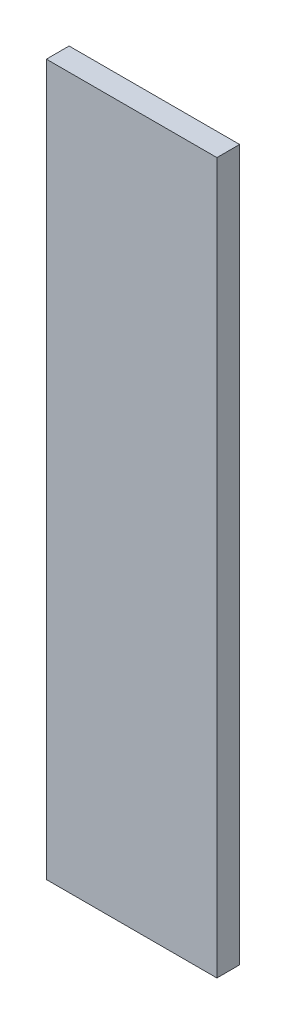
SolidWorks part; units mm, degrees
ref_plane "Alzado" through (0, 0, 0) normal (0, 0, 1) x (1, 0, 0)
ref_plane "Planta" through (0, 0, 0) normal (0, 1, 0) x (1, 0, 0)
ref_plane "Vista lateral" through (0, 0, 0) normal (1, 0, 0) x (0, 0, -1)
sketch "Croquis1" plane through (0, 0, 0) normal (0, 0, 1) x (1, 0, 0)
  line L1 (0, 0) -> (60, 0)
  line L2 (0, 0) -> (0, 250)
  line L3 (0, 250) -> (60, 250)
  line L4 (60, 0) -> (60, 250)
  dimension "D1" = 250
  dimension "D2" = 60
extrude "Saliente-Extruir1" add sketch "Croquis1" along normal blind 8
